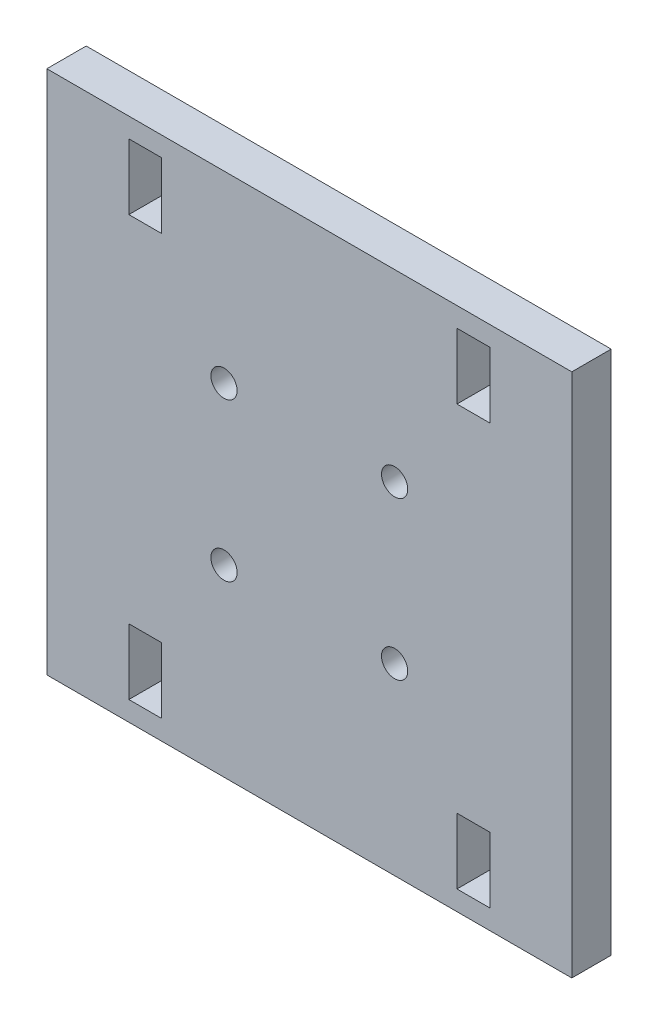
SolidWorks part; units mm, degrees
material "Acrílico (Impacto medio-alto)"
ref_plane "Alzado" through (0, 0, 0) normal (0, 0, 1) x (1, 0, 0)
ref_plane "Planta" through (0, 0, 0) normal (0, 1, 0) x (1, 0, 0)
ref_plane "Vista lateral" through (0, 0, 0) normal (1, 0, 0) x (0, 0, -1)
sketch "Sketch1" plane through (0, 0, 0) normal (0, 0, 1) x (1, 0, 0)
  line L0 (0, -1000) -> (0, 49000) construction
  line L5 (-1000, 0) -> (49000, 0) construction
  line L7 (-20, -20) -> (20, -20)
  line L8 (-20, -20) -> (-20, 20)
  line L9 (-20, 20) -> (20, 20)
  line L10 (20, -20) -> (20, 20)
  line L11 (-20, -20) -> (20, 20) construction
  line L12 (-20, 20) -> (20, -20) construction
  circle A0 centre (6.5, -6) radius 1
  circle A1 centre (-6.5, -6) radius 1
  circle A2 centre (6.5, 6) radius 1
  circle A3 centre (-6.5, 6) radius 1
  point P14 (0, 0)
  dimension "D3" = 2
  dimension "D1" = 6
  dimension "D2" = 6.5
  dimension "D4" = 40
  dimension "D5" = 40
extrude "Boss-Extrude1" add sketch "Sketch1" along normal blind 3
sketch "Sketch2" plane through (0, 0, 3) normal (0, 0, 1) x (1, 0, 0)
  line L0 (0, -1000) -> (0, 49000) construction
  line L1 (11.25, 18.5) -> (13.75, 18.5)
  line L2 (11.25, 18.5) -> (11.25, 13.5)
  line L3 (11.25, 13.5) -> (13.75, 13.5)
  line L4 (13.75, 18.5) -> (13.75, 13.5)
  line L5 (11.25, 18.5) -> (13.75, 13.5) construction
  line L6 (11.25, 13.5) -> (13.75, 18.5) construction
  line L7 (-1000, 0) -> (49000, 0) construction
  line L8 (20, 20) -> (-20, 20) construction
  line L9 (11.25, -13.5) -> (13.75, -13.5)
  line L10 (13.75, -18.5) -> (13.75, -13.5)
  line L11 (11.25, -18.5) -> (13.75, -18.5)
  line L12 (11.25, -18.5) -> (11.25, -13.5)
  line L13 (-11.25, -18.5) -> (-13.75, -18.5)
  line L14 (-11.25, -18.5) -> (-11.25, -13.5)
  line L15 (-13.75, -18.5) -> (-13.75, -13.5)
  line L16 (-11.25, -13.5) -> (-13.75, -13.5)
  line L17 (-11.25, 13.5) -> (-13.75, 13.5)
  line L18 (-11.25, 18.5) -> (-13.75, 18.5)
  line L19 (-11.25, 18.5) -> (-11.25, 13.5)
  line L20 (-13.75, 18.5) -> (-13.75, 13.5)
  point P0 (12.5, 16)
  dimension "D1" = 12.5
  dimension "D2" = 4
  dimension "D3" = 5
  dimension "D4" = 2.5
extrude "Cut-Extrude1" cut sketch "Sketch2" against normal blind 5
